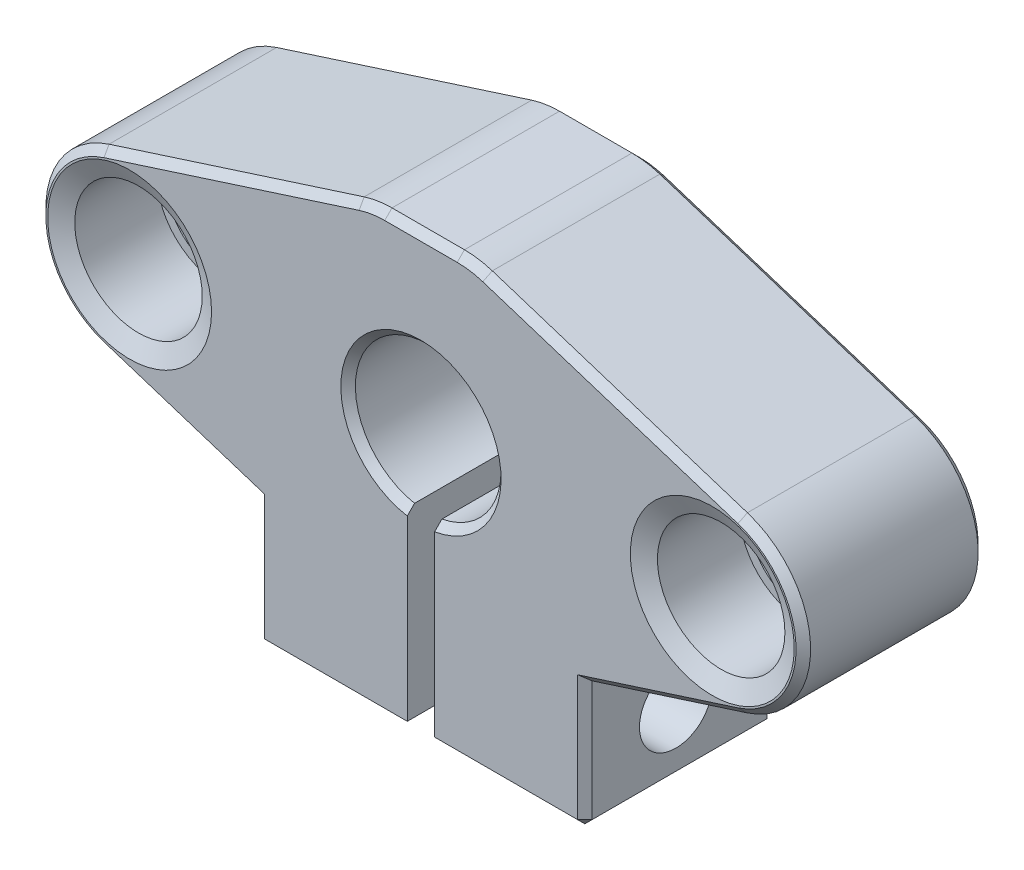
SolidWorks part; units mm, degrees
ref_plane "Front Plane" through (0, 0, 0) normal (0, 0, 1) x (1, 0, 0)
ref_plane "Top Plane" through (0, 0, 0) normal (0, 1, 0) x (1, 0, 0)
ref_plane "Right Plane" through (0, 0, 0) normal (1, 0, 0) x (0, 0, -1)
ref_plane "Plane1" through (0, 0, 10) normal (0, 0, 1) x (1, 0, 0)
sketch "Sketch1" plane through (0, 0, 10) normal (0, 0, 1) x (1, 0, 0)
  line L0 (-9, -7.5) -> (-9, -14.5)
  line L1 (-9, -14.5) -> (9, -14.5)
  line L2 (9, -14.5) -> (9, -7.5)
  line L3 (9, -7.5) -> (17.5291, -4.7605)
  line L4 (17.5291, 4.7605) -> (2.7734, 9.5)
  line L5 (2.7734, 9.5) -> (-2.7734, 9.5)
  line L6 (-2.7734, 9.5) -> (-17.5291, 4.7605)
  line L7 (-17.5291, -4.7605) -> (-9, -7.5)
  arc A0 (17.5291, -4.7605) -> (17.5291, 4.7605) centre (16, 0) ccw
  arc A1 (-17.5291, 4.7605) -> (-17.5291, -4.7605) centre (-16, 0) ccw
extrude "Boss-Extrude1" add sketch "Sketch1" against normal blind 10
sketch "Sketch2" plane through (0, 0, 0) normal (0, 0, -1) x (-1, 0, 0)
  line L0 (9, -11.2309) -> (9, -10.7691)
  line L1 (9, -10.7691) -> (8.6, -11)
  line L2 (8.6, -11) -> (9, -11.2309)
extrude "Cut-Extrude1" cut sketch "Sketch2" against normal through all
sketch "Sketch3" plane through (0, 0, 0) normal (0, 0, -1) x (-1, 0, 0)
  line L0 (0.75, -14.5) -> (0.75, -3.9291)
  line L1 (-0.75, -3.9291) -> (-0.75, -14.5)
  line L2 (-0.75, -14.5) -> (0.75, -14.5)
  arc A0 (0.75, -3.9291) -> (-0.75, -3.9291) centre (0, 0) cw
extrude "Cut-Extrude2" cut sketch "Sketch3" against normal through all
ref_plane "Plane2" through (0, 0, 0) normal (0, -1, 0) x (1, 0, 0)
sketch "Sketch4" plane through (0, 0, 0) normal (0, -1, 0) x (1, 0, 0)
  line L0 (4, 10) -> (0, 10)
  line L1 (0, 10) -> (0, 0)
  line L2 (0, 0) -> (4, 0)
  line L3 (4, 0) -> (4, 10)
  line L4 (0, 10) -> (0, 0) construction
revolve "Cut-Revolve1" cut sketch "Sketch4" angle 360 about L4 reverse direction yes
hole_wizard "Ø4.0 (4) Diameter Hole1" positions "Sketch6" profile "Sketch5" hole size "Ø4.0" standard "ANSI Metric"
sketch "Sketch6" plane through (-0.75, 0, 0) normal (1, 0, 0) x (0, 0, -1)
  point P0 (-5, -11)
sketch "Sketch5" plane through (-0.75, -11, 5) normal (0, 1, 0) x (0, 0, -1)
  line L0 (0, 0) -> (0, 20.25)
  line L1 (0, 20.25) -> (2, 20.25)
  line L2 (2, 20.25) -> (2, 0)
  line L5 (2, 0) -> (0, 0)
  line L11 (0, -6.35) -> (0, 107.95) construction
  dimension "Thru Hole Dia." = 4
  dimension "Thru Hole Depth" = 20.25
hole_wizard "Ø4.0 (4) Diameter Hole2" positions "Sketch8" profile "Sketch7" hole size "Ø4.0" standard "ANSI Metric"
sketch "Sketch8" plane through (0.75, 0, 0) normal (-1, 0, 0) x (0, 0, 1)
  point P0 (5, -11)
sketch "Sketch7" plane through (0.75, -11, 5) normal (0, 1, 0) x (0, 0, 1)
  line L0 (0, 0) -> (0, 20.25)
  line L1 (0, 20.25) -> (2, 20.25)
  line L2 (2, 20.25) -> (2, 0)
  line L5 (2, 0) -> (0, 0)
  line L11 (0, -6.35) -> (0, 107.95) construction
  dimension "Thru Hole Dia." = 4
  dimension "Thru Hole Depth" = 20.25
hole_wizard "M7x1.0 Tapped Hole1" positions "Sketch10" profile "Sketch9" tap size "M7x1.0" standard "ANSI Metric"
sketch "Sketch10" plane through (0, 0, 10) normal (0, 0, 1) x (1, 0, 0)
  point P0 (-16, 0)
  point P1 (16, 0)
sketch "Sketch9" plane through (-16, 0, 10) normal (1, 0, 0) x (0, -1, 0)
  line L0 (0, 0) -> (0, 10)
  line L1 (0, 10) -> (3, 10)
  line L3 (3, 10) -> (3, 5)
  line L4 (3, 5) -> (3.5, 5)
  line L5 (3.5, 5) -> (3.5, 0)
  line L7 (3.5, 0) -> (0, 0)
  line L11 (0, -6.35) -> (0, 107.95) construction
  dimension "Thru Tap Drill Dia." = 6
  dimension "Thru Tap Drill Depth" = 10
  dimension "Thread Major Dia." = 7
  dimension "Thread Depth" = 5
fillet "Fillet1" radius 5 2 edges at (2.7734, 9.5, 5) (-2.7734, 9.5, 5) tangent propagation no
chamfer "Chamfer1" distance 1 angle 26 2 edges at (19.5, 0, 10) (-12.5, 0, 10) first distance on face at (-12.5, 0, 10)
chamfer "Chamfer2" distance 0.4 angle 45 31 edges at (13.2645, -6.1302, 0) (21, 0, 0) (10.5241, 7.0105, 0) (2.7639, 9.4398, 0) (0, 9.5, 0) (-2.7639, 9.4398, 0) (-10.5241, 7.0105, 0) (-13.2645, -6.1302, 0) (-21, 0, 0) (-9, -9.1345, 10) (-13.2645, -6.1302, 10) (-21, 0, 10) (-10.5241, 7.0105, 10) (-2.7639, 9.4398, 10) (0, 9.5, 10) (2.7639, 9.4398, 10) (10.5241, 7.0105, 10) (21, 0, 10) (13.2645, -6.1302, 10) (9, -11, 10) (4.875, -14.5, 10) (9, -14.5, 5) (0.75, -14.5, 5) (4.875, -14.5, 0) (0, 4, 10) (-9, -12.8655, 10) (-9, -14.5, 5) (-4.875, -14.5, 0) (-0.75, -14.5, 5) (-4.875, -14.5, 10) (0, 4, 0)
chamfer "Chamfer3" distance 1 angle 26 2 edges at (-13, 0, 0) (19, 0, 0) first distance on face at (-13, 0, 0)
